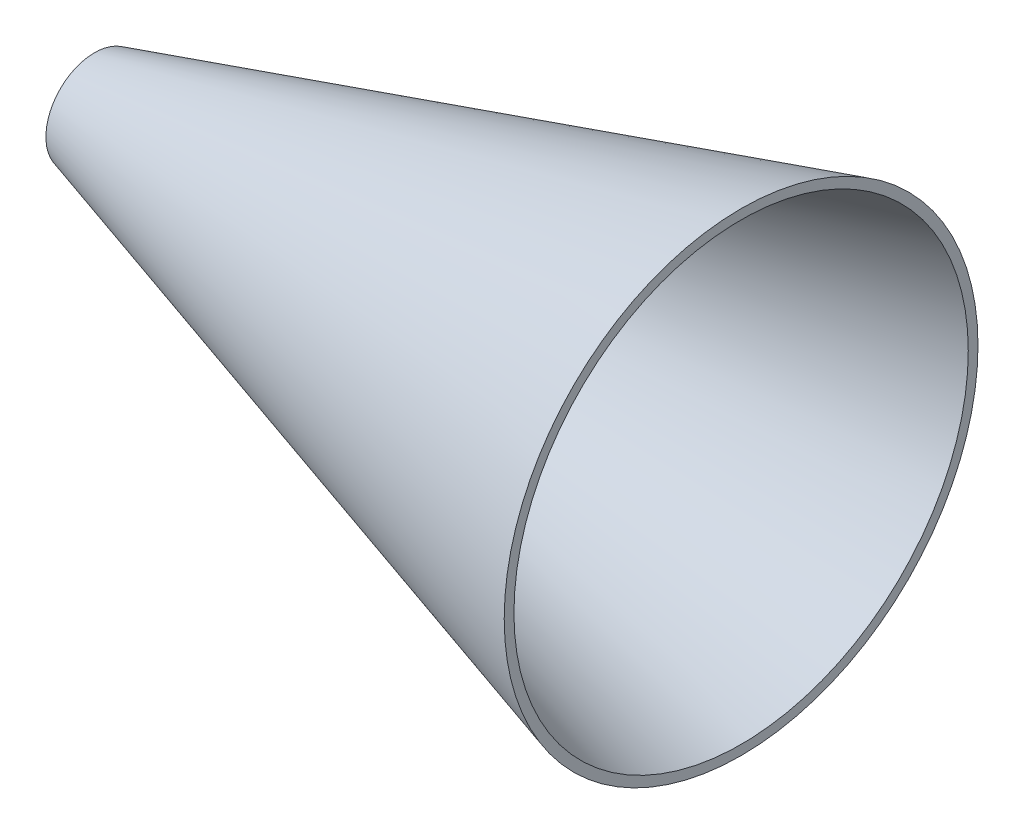
SolidWorks part; units mm, degrees
material "1060 Alloy"
ref_plane "Front Plane" through (0, 0, 0) normal (0, 0, 1) x (1, 0, 0)
ref_plane "Top Plane" through (0, 0, 0) normal (0, 1, 0) x (1, 0, 0)
ref_plane "Right Plane" through (0, 0, 0) normal (1, 0, 0) x (0, 0, -1)
ref_axis "X-axis" through (-88.99, 0, 0) along (1, 0, 0)
ref_axis "Y-axis" through (0, 55, 0) along (0, -1, 0)
ref_axis "Z-axis" through (0, 0, -88.99) along (0, 0, 1)
sketch "Sketch1" plane through (0, 0, 0) normal (0, 0, 1) x (1, 0, 0)
  line L0 (0, 0) -> (0, 1.27)
  line L1 (0, 1.27) -> (16.891, 6.1887)
  line L2 (16.891, 6.1887) -> (16.891, 5.9347)
  line L3 (16.891, 5.9347) -> (0.254, 1.09)
  line L4 (0.254, 1.09) -> (0.254, 0)
  line L5 (0.254, 0) -> (0, 0)
  dimension "D1" = 16.891
  dimension "D2" = 0.254
  dimension "D3" = 0.254
  dimension "D4" = 1.27
revolve "Revolve1" add sketch "Sketch1" angle 360 about axis through (-88.99, 0, 0) along (1, 0, 0)
sketch "Sketch2" plane through (0, 0, 0) normal (-1, 0, 0) x (0, 0, 1)
  circle A0 centre (0, 0) radius 1.016
  circle A1 centre (0, 0) radius 1.27 construction
  dimension "D1" = 0.254
extrude "Cut-Extrude1" cut sketch "Sketch2" against normal blind 2.54
